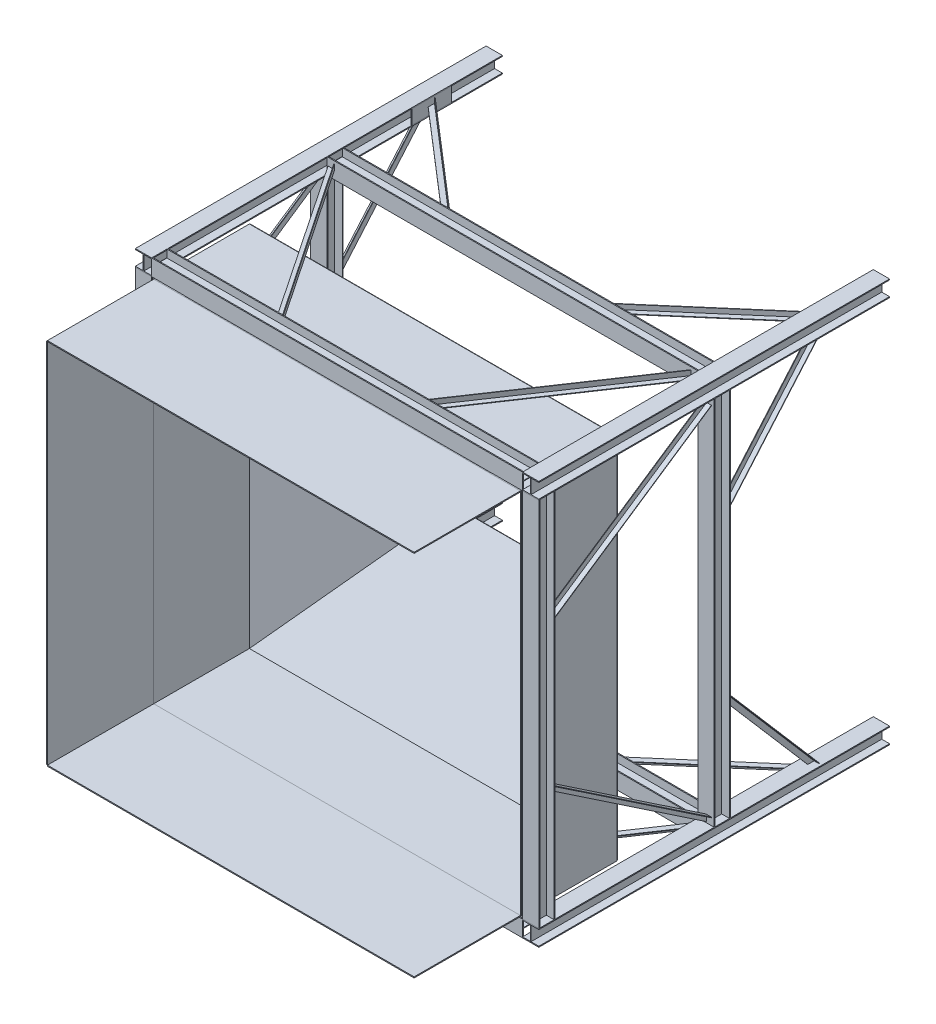
SolidWorks part; units mm, degrees
other "DetailItem1"
other "DetailItem2"
other "DetailItem3"
other "DetailItem4"
other "DetailItem5"
other "DetailItem6"
other "DetailItem7"
other "DetailItem8"
other "DetailItem9"
other "DetailItem10"
other "DetailItem11"
other "DetailItem12"
other "DetailItem13"
other "DetailItem14"
other "DetailItem15"
other "DetailItem16"
other "DetailItem17"
other "DetailItem18"
other "DetailItem19"
other "DetailItem20"
other "DetailItem21"
other "DetailItem22"
other "DetailItem23"
other "DetailItem24"
other "DetailItem25"
other "DetailItem26"
other "DetailItem27"
other "DetailItem28"
other "DetailItem29"
other "DetailItem30"
other "DetailItem31"
other "DetailItem32"
other "DetailItem33"
other "DetailItem34"
other "DetailItem35"
other "DetailItem36"
other "DetailItem37"
other "DetailItem38"
other "DetailItem39"
other "DetailItem40"
other "DetailItem41"
other "DetailItem42"
other "DetailItem43"
other "DetailItem44"
other "DetailItem45"
other "DetailItem46"
other "DetailItem47"
other "DetailItem48"
other "DetailItem49"
other "DetailItem50"
other "DetailItem51"
other "DetailItem52"
other "DetailItem53"
other "DetailItem54"
other "DetailItem55"
other "DetailItem56"
other "DetailItem57"
other "DetailItem58"
other "DetailItem59"
other "DetailItem60"
other "DetailItem61"
other "DetailItem62"
other "DetailItem63"
other "DetailItem64"
other "DetailItem65"
other "DetailItem66"
other "DetailItem67"
other "DetailItem68"
other "DetailItem69"
other "DetailItem70"
other "DetailItem71"
other "DetailItem72"
other "DetailItem73"
other "Carpeta de soldadura"
other "Cordón de soldadura1"
other "Soldadura Viga H carga 1650 B"
other "Soldadura Viga H carga 3300 A"
other "Soldadura Viga H carga 3300 B"
other "Soldadura asiento a tolva carga"
other "Soldadura asiento a bastidor carga"
other "Soldadura Viga H fondo 1650 A"
other "Soldadura Viga H fondo 1650 B"
other "Soldadura Viga H fondo 3300 A"
other "Soldadura Viga H fondo 3300 B"
other "Soldadura asiento a tolva fondo"
other "Soldadura asiento a bastidor fondo"
other "Soldadura Viga H izquierda 1650 A"
other "Soldadura Viga H izquierda 1650 B"
other "Soldadura Viga H izquierda 3300 A"
other "Soldadura Viga H izquierda 3300 B"
other "Soldadura asiento a tolva izquierda"
other "Soldadura asiento a bastidor izquierda"
other "Soldadura Viga H derecha 1650 A"
other "Soldadura Viga H derecha 1650 B"
other "Soldadura Viga H derecha 3300 A"
other "Soldadura Viga H derecha 3300 B"
other "Soldadura asiento a tolva derecha"
other "Soldadura asiento a bastidor derecha"
other "Soldadura Angular superior carga A inferior"
other "Soldadura Angular superior carga A superior"
other "Soldadura Angular inferior carga A inferior"
other "Soldadura Angular inferior carga A superior"
other "Soldadura Angular superior carga B inferior"
other "Soldadura Angular superior carga B superior"
other "Soldadura Angular inferior carga B inferior"
other "Soldadura Angular inferior carga B superior"
other "Soldadura Angular superior fondo A inferior"
other "Soldadura Angular superior fondo A superior"
other "Soldadura Angular inferior fondo A inferior"
other "Soldadura Angular inferior fondo A superior"
other "Soldadura Angular superior fondo B inferior"
other "Soldadura Angular superior fondo B superior"
other "Soldadura Angular inferior fondo B inferior"
other "Soldadura Angular inferior fondo B superior"
other "Soldadura Angular superior izquierda A inferior"
other "Soldadura Angular superior izquierda A superior"
other "Soldadura Angular inferior izquierda A inferior"
other "Soldadura Angular inferior izquierda A superior"
other "Soldadura Angular superior izquierda B inferior"
other "Soldadura Angular superior izquierda B superior"
other "Soldadura Angular inferior izquierda B inferior"
other "Soldadura Angular inferior izquierda B superior"
other "Soldadura Angular superior derecha A inferior"
other "Soldadura Angular superior derecha A superior"
other "Soldadura Angular inferior derecha A inferior"
other "Soldadura Angular inferior derecha A superior"
other "Soldadura Angular superior derecha B inferior"
other "Soldadura Angular superior derecha B superior"
other "Soldadura Angular inferior derecha B inferior"
other "Soldadura Angular inferior derecha B superior"
other "Soldadura alerón a collar lateral Y negativo"
other "Soldadura esquina del collar lateral Y negativo"
other "Soldadura quiebre del embudo lateral Y negativo"
other "Soldadura arista inclinada lateral Y negativo"
other "Soldadura esquina del collar carga"
other "Soldadura quiebre del embudo carga"
other "Soldadura arista inclinada carga"
other "Soldadura alerón a collar lateral Y positivo"
other "Soldadura esquina del collar lateral Y positivo"
other "Soldadura quiebre del embudo lateral Y positivo"
other "Soldadura arista inclinada lateral Y positivo"
other "Soldadura alerón a collar fondo X negativo"
other "Soldadura esquina del collar fondo X negativo"
other "Soldadura quiebre del embudo fondo X negativo"
other "Soldadura arista inclinada fondo X negativo"
other "Soldadura esquina alerones fondo Y positivo"
other "Soldadura esquina alerones fondo Y negativo"
material "ASTM A36 Steel"
ref_plane "Front Plane" through (0, 0, 0) normal (0, 0, 1) x (1, 0, 0)
ref_plane "Top Plane" through (0, 0, 0) normal (0, 1, 0) x (1, 0, 0)
ref_plane "Right Plane" through (0, 0, 0) normal (1, 0, 0) x (0, 0, -1)
sketch3d "Referencias 1"
  point P0 (0, 0, 0)
  point P1 (0, -190, 0)
  point P2 (200, 0, 0)
ref_plane "Plano de perfil 1 estructura" through (0, 0, 0) normal (0, 0, 1) x (1, 0, 0)
sketch "Contorno Columna H 1" plane through (0, 0, 0) normal (0, 0, 1) x (1, 0, 0)
  line L0 (-1898, -1898) -> (-1745, -1898)
  line L1 (-1745, -1898) -> (-1745, -1889)
  line L2 (-1745, -1889) -> (-1818.25, -1889)
  line L3 (-1818.25, -1889) -> (-1818.25, -1754)
  line L4 (-1818.25, -1754) -> (-1745, -1754)
  line L5 (-1745, -1754) -> (-1745, -1745)
  line L6 (-1745, -1745) -> (-1898, -1745)
  line L7 (-1898, -1745) -> (-1898, -1754)
  line L8 (-1898, -1754) -> (-1824.75, -1754)
  line L9 (-1824.75, -1754) -> (-1824.75, -1889)
  line L10 (-1824.75, -1889) -> (-1898, -1889)
  line L11 (-1898, -1889) -> (-1898, -1898)
extrude "Columna H 1" add sketch "Contorno Columna H 1" along normal blind 3300 separate body
sketch "Contorno Columna H 2" plane through (0, 0, 0) normal (0, 0, 1) x (1, 0, 0)
  line L0 (-1898, 1745) -> (-1745, 1745)
  line L1 (-1745, 1745) -> (-1745, 1754)
  line L2 (-1745, 1754) -> (-1818.25, 1754)
  line L3 (-1818.25, 1754) -> (-1818.25, 1889)
  line L4 (-1818.25, 1889) -> (-1745, 1889)
  line L5 (-1745, 1889) -> (-1745, 1898)
  line L6 (-1745, 1898) -> (-1898, 1898)
  line L7 (-1898, 1898) -> (-1898, 1889)
  line L8 (-1898, 1889) -> (-1824.75, 1889)
  line L9 (-1824.75, 1889) -> (-1824.75, 1754)
  line L10 (-1824.75, 1754) -> (-1898, 1754)
  line L11 (-1898, 1754) -> (-1898, 1745)
extrude "Columna H 2" add sketch "Contorno Columna H 2" along normal blind 3300 separate body
sketch "Contorno Columna H 3" plane through (0, 0, 0) normal (0, 0, 1) x (1, 0, 0)
  line L0 (1745, -1898) -> (1898, -1898)
  line L1 (1898, -1898) -> (1898, -1889)
  line L2 (1898, -1889) -> (1824.75, -1889)
  line L3 (1824.75, -1889) -> (1824.75, -1754)
  line L4 (1824.75, -1754) -> (1898, -1754)
  line L5 (1898, -1754) -> (1898, -1745)
  line L6 (1898, -1745) -> (1745, -1745)
  line L7 (1745, -1745) -> (1745, -1754)
  line L8 (1745, -1754) -> (1818.25, -1754)
  line L9 (1818.25, -1754) -> (1818.25, -1889)
  line L10 (1818.25, -1889) -> (1745, -1889)
  line L11 (1745, -1889) -> (1745, -1898)
extrude "Columna H 3" add sketch "Contorno Columna H 3" along normal blind 3300 separate body
sketch "Contorno Columna H 4" plane through (0, 0, 0) normal (0, 0, 1) x (1, 0, 0)
  line L0 (1745, 1745) -> (1898, 1745)
  line L1 (1898, 1745) -> (1898, 1754)
  line L2 (1898, 1754) -> (1824.75, 1754)
  line L3 (1824.75, 1754) -> (1824.75, 1889)
  line L4 (1824.75, 1889) -> (1898, 1889)
  line L5 (1898, 1889) -> (1898, 1898)
  line L6 (1898, 1898) -> (1745, 1898)
  line L7 (1745, 1898) -> (1745, 1889)
  line L8 (1745, 1889) -> (1818.25, 1889)
  line L9 (1818.25, 1889) -> (1818.25, 1754)
  line L10 (1818.25, 1754) -> (1745, 1754)
  line L11 (1745, 1754) -> (1745, 1745)
extrude "Columna H 4" add sketch "Contorno Columna H 4" along normal blind 3300 separate body
sketch3d "Referencias 2"
  point P0 (-1745, 0, 0)
  point P1 (-1745, 190, 0)
  point P2 (-1745, 0, 200)
ref_plane "Plano de perfil 2 estructura" through (-1745, 0, 0) normal (1, 0, 0) x (0, 0, -1)
sketch "Contorno Viga H carga 1650" plane through (-1745, 0, 0) normal (1, 0, 0) x (0, 0, -1)
  line L0 (-1497, -1745) -> (-1497, -1898)
  line L1 (-1497, -1898) -> (-1506, -1898)
  line L2 (-1506, -1898) -> (-1506, -1824.75)
  line L3 (-1506, -1824.75) -> (-1641, -1824.75)
  line L4 (-1641, -1824.75) -> (-1641, -1898)
  line L5 (-1641, -1898) -> (-1650, -1898)
  line L6 (-1650, -1898) -> (-1650, -1745)
  line L7 (-1650, -1745) -> (-1641, -1745)
  line L8 (-1641, -1745) -> (-1641, -1818.25)
  line L9 (-1641, -1818.25) -> (-1506, -1818.25)
  line L10 (-1506, -1818.25) -> (-1506, -1745)
  line L11 (-1506, -1745) -> (-1497, -1745)
extrude "Viga H carga 1650" add sketch "Contorno Viga H carga 1650" along normal blind 3490 separate body
sketch "Contorno Viga H carga 3300" plane through (-1745, 0, 0) normal (1, 0, 0) x (0, 0, -1)
  line L0 (-3147, -1745) -> (-3147, -1898)
  line L1 (-3147, -1898) -> (-3156, -1898)
  line L2 (-3156, -1898) -> (-3156, -1824.75)
  line L3 (-3156, -1824.75) -> (-3291, -1824.75)
  line L4 (-3291, -1824.75) -> (-3291, -1898)
  line L5 (-3291, -1898) -> (-3300, -1898)
  line L6 (-3300, -1898) -> (-3300, -1745)
  line L7 (-3300, -1745) -> (-3291, -1745)
  line L8 (-3291, -1745) -> (-3291, -1818.25)
  line L9 (-3291, -1818.25) -> (-3156, -1818.25)
  line L10 (-3156, -1818.25) -> (-3156, -1745)
  line L11 (-3156, -1745) -> (-3147, -1745)
extrude "Viga H carga 3300" add sketch "Contorno Viga H carga 3300" along normal blind 3490 separate body
sketch "Contorno Cierre columna carga A" plane through (-1745, 0, 0) normal (1, 0, 0) x (0, 0, -1)
  line L0 (-480, -1754) -> (-480, -1889)
  line L1 (-480, -1889) -> (-850, -1889)
  line L2 (-850, -1889) -> (-850, -1754)
  line L3 (-850, -1754) -> (-480, -1754)
extrude "Cierre columna carga A" add sketch "Contorno Cierre columna carga A" against normal blind 8 separate body
sketch3d "Referencias 3"
  point P0 (0, -1821.5, 0)
  point P1 (-190, -1821.5, 0)
  point P2 (0, -1821.5, 200)
ref_plane "Plano de perfil 3 estructura" through (0, -1821.5, 0) normal (0, 1, 0) x (1, 0, 0)
sketch "Contorno Ala plana Angular superior carga A" plane through (0, -1821.5, 0) normal (0, 1, 0) x (1, 0, 0)
  line L0 (-1674.8701, -1650) -> (-1735.1299, -1650)
  line L1 (-1735.1299, -1650) -> (-728.1299, -3147)
  line L2 (-728.1299, -3147) -> (-667.8701, -3147)
  line L3 (-667.8701, -3147) -> (-1674.8701, -1650)
extrude "Ala plana Angular superior carga A" add sketch "Contorno Ala plana Angular superior carga A" against normal blind 5 separate body
sketch3d "Referencias 4"
  point P0 (0, -1826.5, 0)
  point P1 (-190, -1826.5, 0)
  point P2 (0, -1826.5, 200)
ref_plane "Plano de perfil 4 estructura" through (0, -1826.5, 0) normal (0, 1, 0) x (1, 0, 0)
sketch "Contorno Retorno Angular superior carga A" plane through (0, -1826.5, 0) normal (0, 1, 0) x (1, 0, 0)
  line L0 (-1674.8701, -1650) -> (-1680.8961, -1650)
  line L1 (-1680.8961, -1650) -> (-673.8961, -3147)
  line L2 (-673.8961, -3147) -> (-667.8701, -3147)
  line L3 (-667.8701, -3147) -> (-1674.8701, -1650)
extrude "Retorno Angular superior carga A" add sketch "Contorno Retorno Angular superior carga A" against normal blind 45 separate body
combine bodies "Angular superior carga A" operation type add bodies to combine 108 109
sketch "Contorno Ala plana Angular inferior carga A" plane through (0, -1821.5, 0) normal (0, 1, 0) x (1, 0, 0)
  line L0 (-1745, -631.991) -> (-1745, -698.009)
  line L1 (-1745, -698.009) -> (-818.2856, -1497)
  line L2 (-818.2856, -1497) -> (-741.7144, -1497)
  line L3 (-741.7144, -1497) -> (-1745, -631.991)
extrude "Ala plana Angular inferior carga A" add sketch "Contorno Ala plana Angular inferior carga A" against normal blind 5 separate body
sketch "Contorno Retorno Angular inferior carga A" plane through (0, -1826.5, 0) normal (0, 1, 0) x (1, 0, 0)
  line L0 (-1745, -631.991) -> (-1745, -638.5928)
  line L1 (-1745, -638.5928) -> (-749.3715, -1497)
  line L2 (-749.3715, -1497) -> (-741.7144, -1497)
  line L3 (-741.7144, -1497) -> (-1745, -631.991)
extrude "Retorno Angular inferior carga A" add sketch "Contorno Retorno Angular inferior carga A" against normal blind 45 separate body
combine bodies "Angular inferior carga A" operation type add bodies to combine 111 112
sketch3d "Referencias 5"
  point P0 (1745, 0, 0)
  point P1 (1745, 190, 0)
  point P2 (1745, 0, 200)
ref_plane "Plano de perfil 5 estructura" through (1745, 0, 0) normal (1, 0, 0) x (0, 0, -1)
sketch "Contorno Cierre columna carga B" plane through (1745, 0, 0) normal (1, 0, 0) x (0, 0, -1)
  line L0 (-480, -1754) -> (-480, -1889)
  line L1 (-480, -1889) -> (-850, -1889)
  line L2 (-850, -1889) -> (-850, -1754)
  line L3 (-850, -1754) -> (-480, -1754)
extrude "Cierre columna carga B" add sketch "Contorno Cierre columna carga B" along normal blind 8 separate body
sketch "Contorno Ala plana Angular superior carga B" plane through (0, -1821.5, 0) normal (0, 1, 0) x (1, 0, 0)
  line L0 (1674.8701, -1650) -> (1735.1299, -1650)
  line L1 (1735.1299, -1650) -> (728.1299, -3147)
  line L2 (728.1299, -3147) -> (667.8701, -3147)
  line L3 (667.8701, -3147) -> (1674.8701, -1650)
extrude "Ala plana Angular superior carga B" add sketch "Contorno Ala plana Angular superior carga B" against normal blind 5 separate body
sketch "Contorno Retorno Angular superior carga B" plane through (0, -1826.5, 0) normal (0, 1, 0) x (1, 0, 0)
  line L0 (1674.8701, -1650) -> (1680.8961, -1650)
  line L1 (1680.8961, -1650) -> (673.8961, -3147)
  line L2 (673.8961, -3147) -> (667.8701, -3147)
  line L3 (667.8701, -3147) -> (1674.8701, -1650)
extrude "Retorno Angular superior carga B" add sketch "Contorno Retorno Angular superior carga B" against normal blind 45 separate body
combine bodies "Angular superior carga B" operation type add bodies to combine 115 116
sketch "Contorno Ala plana Angular inferior carga B" plane through (0, -1821.5, 0) normal (0, 1, 0) x (1, 0, 0)
  line L0 (1745, -631.991) -> (1745, -698.009)
  line L1 (1745, -698.009) -> (818.2856, -1497)
  line L2 (818.2856, -1497) -> (741.7144, -1497)
  line L3 (741.7144, -1497) -> (1745, -631.991)
extrude "Ala plana Angular inferior carga B" add sketch "Contorno Ala plana Angular inferior carga B" against normal blind 5 separate body
sketch "Contorno Retorno Angular inferior carga B" plane through (0, -1826.5, 0) normal (0, 1, 0) x (1, 0, 0)
  line L0 (1745, -631.991) -> (1745, -638.5928)
  line L1 (1745, -638.5928) -> (749.3715, -1497)
  line L2 (749.3715, -1497) -> (741.7144, -1497)
  line L3 (741.7144, -1497) -> (1745, -631.991)
extrude "Retorno Angular inferior carga B" add sketch "Contorno Retorno Angular inferior carga B" against normal blind 45 separate body
combine bodies "Angular inferior carga B" operation type add bodies to combine 118 119
sketch3d "Referencias 6"
  point P0 (0, 0, 3281.475)
  point P1 (0, -190, 3281.475)
  point P2 (200, 0, 3281.475)
ref_plane "Plano de perfil 6 estructura" through (0, 0, 3281.475) normal (0, 0, 1) x (1, 0, 0)
sketch "Contorno Asiento soldado carga" plane through (0, 0, 3281.475) normal (0, 0, 1) x (1, 0, 0)
  line L0 (-1450, -1734.525) -> (1450, -1734.525)
  line L1 (1450, -1734.525) -> (1450, -1818.25)
  line L2 (1450, -1818.25) -> (-1450, -1818.25)
  line L3 (-1450, -1818.25) -> (-1450, -1734.525)
extrude "Asiento soldado carga" add sketch "Contorno Asiento soldado carga" along normal blind 9.525 separate body
sketch "Contorno Viga H fondo 1650" plane through (-1745, 0, 0) normal (1, 0, 0) x (0, 0, -1)
  line L0 (-1497, 1745) -> (-1497, 1898)
  line L1 (-1497, 1898) -> (-1506, 1898)
  line L2 (-1506, 1898) -> (-1506, 1824.75)
  line L3 (-1506, 1824.75) -> (-1641, 1824.75)
  line L4 (-1641, 1824.75) -> (-1641, 1898)
  line L5 (-1641, 1898) -> (-1650, 1898)
  line L6 (-1650, 1898) -> (-1650, 1745)
  line L7 (-1650, 1745) -> (-1641, 1745)
  line L8 (-1641, 1745) -> (-1641, 1818.25)
  line L9 (-1641, 1818.25) -> (-1506, 1818.25)
  line L10 (-1506, 1818.25) -> (-1506, 1745)
  line L11 (-1506, 1745) -> (-1497, 1745)
extrude "Viga H fondo 1650" add sketch "Contorno Viga H fondo 1650" along normal blind 3490 separate body
sketch "Contorno Viga H fondo 3300" plane through (-1745, 0, 0) normal (1, 0, 0) x (0, 0, -1)
  line L0 (-3147, 1745) -> (-3147, 1898)
  line L1 (-3147, 1898) -> (-3156, 1898)
  line L2 (-3156, 1898) -> (-3156, 1824.75)
  line L3 (-3156, 1824.75) -> (-3291, 1824.75)
  line L4 (-3291, 1824.75) -> (-3291, 1898)
  line L5 (-3291, 1898) -> (-3300, 1898)
  line L6 (-3300, 1898) -> (-3300, 1745)
  line L7 (-3300, 1745) -> (-3291, 1745)
  line L8 (-3291, 1745) -> (-3291, 1818.25)
  line L9 (-3291, 1818.25) -> (-3156, 1818.25)
  line L10 (-3156, 1818.25) -> (-3156, 1745)
  line L11 (-3156, 1745) -> (-3147, 1745)
extrude "Viga H fondo 3300" add sketch "Contorno Viga H fondo 3300" along normal blind 3490 separate body
sketch "Contorno Cierre columna fondo A" plane through (-1745, 0, 0) normal (1, 0, 0) x (0, 0, -1)
  line L0 (-480, 1754) -> (-480, 1889)
  line L1 (-480, 1889) -> (-850, 1889)
  line L2 (-850, 1889) -> (-850, 1754)
  line L3 (-850, 1754) -> (-480, 1754)
extrude "Cierre columna fondo A" add sketch "Contorno Cierre columna fondo A" against normal blind 8 separate body
sketch3d "Referencias 7"
  point P0 (0, 1821.5, 0)
  point P1 (-190, 1821.5, 0)
  point P2 (0, 1821.5, 200)
ref_plane "Plano de perfil 7 estructura" through (0, 1821.5, 0) normal (0, 1, 0) x (1, 0, 0)
sketch "Contorno Ala plana Angular superior fondo A" plane through (0, 1821.5, 0) normal (0, 1, 0) x (1, 0, 0)
  line L0 (-1674.8701, -1650) -> (-1735.1299, -1650)
  line L1 (-1735.1299, -1650) -> (-728.1299, -3147)
  line L2 (-728.1299, -3147) -> (-667.8701, -3147)
  line L3 (-667.8701, -3147) -> (-1674.8701, -1650)
extrude "Ala plana Angular superior fondo A" add sketch "Contorno Ala plana Angular superior fondo A" along normal blind 5 separate body
sketch3d "Referencias 8"
  point P0 (0, 1826.5, 0)
  point P1 (-190, 1826.5, 0)
  point P2 (0, 1826.5, 200)
ref_plane "Plano de perfil 8 estructura" through (0, 1826.5, 0) normal (0, 1, 0) x (1, 0, 0)
sketch "Contorno Retorno Angular superior fondo A" plane through (0, 1826.5, 0) normal (0, 1, 0) x (1, 0, 0)
  line L0 (-1674.8701, -1650) -> (-1680.8961, -1650)
  line L1 (-1680.8961, -1650) -> (-673.8961, -3147)
  line L2 (-673.8961, -3147) -> (-667.8701, -3147)
  line L3 (-667.8701, -3147) -> (-1674.8701, -1650)
extrude "Retorno Angular superior fondo A" add sketch "Contorno Retorno Angular superior fondo A" along normal blind 45 separate body
combine bodies "Angular superior fondo A" operation type add bodies to combine 125 126
sketch "Contorno Ala plana Angular inferior fondo A" plane through (0, 1821.5, 0) normal (0, 1, 0) x (1, 0, 0)
  line L0 (-1745, -631.991) -> (-1745, -698.009)
  line L1 (-1745, -698.009) -> (-818.2856, -1497)
  line L2 (-818.2856, -1497) -> (-741.7144, -1497)
  line L3 (-741.7144, -1497) -> (-1745, -631.991)
extrude "Ala plana Angular inferior fondo A" add sketch "Contorno Ala plana Angular inferior fondo A" along normal blind 5 separate body
sketch "Contorno Retorno Angular inferior fondo A" plane through (0, 1826.5, 0) normal (0, 1, 0) x (1, 0, 0)
  line L0 (-1745, -631.991) -> (-1745, -638.5928)
  line L1 (-1745, -638.5928) -> (-749.3715, -1497)
  line L2 (-749.3715, -1497) -> (-741.7144, -1497)
  line L3 (-741.7144, -1497) -> (-1745, -631.991)
extrude "Retorno Angular inferior fondo A" add sketch "Contorno Retorno Angular inferior fondo A" along normal blind 45 separate body
combine bodies "Angular inferior fondo A" operation type add bodies to combine 128 129
sketch "Contorno Cierre columna fondo B" plane through (1745, 0, 0) normal (1, 0, 0) x (0, 0, -1)
  line L0 (-480, 1754) -> (-480, 1889)
  line L1 (-480, 1889) -> (-850, 1889)
  line L2 (-850, 1889) -> (-850, 1754)
  line L3 (-850, 1754) -> (-480, 1754)
extrude "Cierre columna fondo B" add sketch "Contorno Cierre columna fondo B" along normal blind 8 separate body
sketch "Contorno Ala plana Angular superior fondo B" plane through (0, 1821.5, 0) normal (0, 1, 0) x (1, 0, 0)
  line L0 (1674.8701, -1650) -> (1735.1299, -1650)
  line L1 (1735.1299, -1650) -> (728.1299, -3147)
  line L2 (728.1299, -3147) -> (667.8701, -3147)
  line L3 (667.8701, -3147) -> (1674.8701, -1650)
extrude "Ala plana Angular superior fondo B" add sketch "Contorno Ala plana Angular superior fondo B" along normal blind 5 separate body
sketch "Contorno Retorno Angular superior fondo B" plane through (0, 1826.5, 0) normal (0, 1, 0) x (1, 0, 0)
  line L0 (1674.8701, -1650) -> (1680.8961, -1650)
  line L1 (1680.8961, -1650) -> (673.8961, -3147)
  line L2 (673.8961, -3147) -> (667.8701, -3147)
  line L3 (667.8701, -3147) -> (1674.8701, -1650)
extrude "Retorno Angular superior fondo B" add sketch "Contorno Retorno Angular superior fondo B" along normal blind 45 separate body
combine bodies "Angular superior fondo B" operation type add bodies to combine 132 133
sketch "Contorno Ala plana Angular inferior fondo B" plane through (0, 1821.5, 0) normal (0, 1, 0) x (1, 0, 0)
  line L0 (1745, -631.991) -> (1745, -698.009)
  line L1 (1745, -698.009) -> (818.2856, -1497)
  line L2 (818.2856, -1497) -> (741.7144, -1497)
  line L3 (741.7144, -1497) -> (1745, -631.991)
extrude "Ala plana Angular inferior fondo B" add sketch "Contorno Ala plana Angular inferior fondo B" along normal blind 5 separate body
sketch "Contorno Retorno Angular inferior fondo B" plane through (0, 1826.5, 0) normal (0, 1, 0) x (1, 0, 0)
  line L0 (1745, -631.991) -> (1745, -638.5928)
  line L1 (1745, -638.5928) -> (749.3715, -1497)
  line L2 (749.3715, -1497) -> (741.7144, -1497)
  line L3 (741.7144, -1497) -> (1745, -631.991)
extrude "Retorno Angular inferior fondo B" add sketch "Contorno Retorno Angular inferior fondo B" along normal blind 45 separate body
combine bodies "Angular inferior fondo B" operation type add bodies to combine 135 136
sketch "Contorno Asiento soldado fondo" plane through (0, 0, 3281.475) normal (0, 0, 1) x (1, 0, 0)
  line L0 (-1450, 1734.525) -> (1450, 1734.525)
  line L1 (1450, 1734.525) -> (1450, 1818.25)
  line L2 (1450, 1818.25) -> (-1450, 1818.25)
  line L3 (-1450, 1818.25) -> (-1450, 1734.525)
extrude "Asiento soldado fondo" add sketch "Contorno Asiento soldado fondo" along normal blind 9.525 separate body
sketch3d "Referencias 9"
  point P0 (0, -1745, 0)
  point P1 (-190, -1745, 0)
  point P2 (0, -1745, 200)
ref_plane "Plano de perfil 9 estructura" through (0, -1745, 0) normal (0, 1, 0) x (1, 0, 0)
sketch "Contorno Viga H izquierda 1650" plane through (0, -1745, 0) normal (0, 1, 0) x (1, 0, 0)
  line L0 (-1745, -1497) -> (-1898, -1497)
  line L1 (-1898, -1497) -> (-1898, -1506)
  line L2 (-1898, -1506) -> (-1824.75, -1506)
  line L3 (-1824.75, -1506) -> (-1824.75, -1641)
  line L4 (-1824.75, -1641) -> (-1898, -1641)
  line L5 (-1898, -1641) -> (-1898, -1650)
  line L6 (-1898, -1650) -> (-1745, -1650)
  line L7 (-1745, -1650) -> (-1745, -1641)
  line L8 (-1745, -1641) -> (-1818.25, -1641)
  line L9 (-1818.25, -1641) -> (-1818.25, -1506)
  line L10 (-1818.25, -1506) -> (-1745, -1506)
  line L11 (-1745, -1506) -> (-1745, -1497)
extrude "Viga H izquierda 1650" add sketch "Contorno Viga H izquierda 1650" along normal blind 3490 separate body
sketch "Contorno Viga H izquierda 3300" plane through (0, -1745, 0) normal (0, 1, 0) x (1, 0, 0)
  line L0 (-1745, -3147) -> (-1898, -3147)
  line L1 (-1898, -3147) -> (-1898, -3156)
  line L2 (-1898, -3156) -> (-1824.75, -3156)
  line L3 (-1824.75, -3156) -> (-1824.75, -3291)
  line L4 (-1824.75, -3291) -> (-1898, -3291)
  line L5 (-1898, -3291) -> (-1898, -3300)
  line L6 (-1898, -3300) -> (-1745, -3300)
  line L7 (-1745, -3300) -> (-1745, -3291)
  line L8 (-1745, -3291) -> (-1818.25, -3291)
  line L9 (-1818.25, -3291) -> (-1818.25, -3156)
  line L10 (-1818.25, -3156) -> (-1745, -3156)
  line L11 (-1745, -3156) -> (-1745, -3147)
extrude "Viga H izquierda 3300" add sketch "Contorno Viga H izquierda 3300" along normal blind 3490 separate body
sketch3d "Referencias 10"
  point P0 (-1821.5, 0, 0)
  point P1 (-1821.5, 190, 0)
  point P2 (-1821.5, 0, 200)
ref_plane "Plano de perfil 10 estructura" through (-1821.5, 0, 0) normal (1, 0, 0) x (0, 0, -1)
sketch "Contorno Ala plana Angular superior izquierda A" plane through (-1821.5, 0, 0) normal (1, 0, 0) x (0, 0, -1)
  line L0 (-1650, -1674.8701) -> (-1650, -1735.1299)
  line L1 (-1650, -1735.1299) -> (-3147, -728.1299)
  line L2 (-3147, -728.1299) -> (-3147, -667.8701)
  line L3 (-3147, -667.8701) -> (-1650, -1674.8701)
extrude "Ala plana Angular superior izquierda A" add sketch "Contorno Ala plana Angular superior izquierda A" against normal blind 5 separate body
sketch3d "Referencias 11"
  point P0 (-1826.5, 0, 0)
  point P1 (-1826.5, 190, 0)
  point P2 (-1826.5, 0, 200)
ref_plane "Plano de perfil 11 estructura" through (-1826.5, 0, 0) normal (1, 0, 0) x (0, 0, -1)
sketch "Contorno Retorno Angular superior izquierda A" plane through (-1826.5, 0, 0) normal (1, 0, 0) x (0, 0, -1)
  line L0 (-1650, -1674.8701) -> (-1650, -1680.8961)
  line L1 (-1650, -1680.8961) -> (-3147, -673.8961)
  line L2 (-3147, -673.8961) -> (-3147, -667.8701)
  line L3 (-3147, -667.8701) -> (-1650, -1674.8701)
extrude "Retorno Angular superior izquierda A" add sketch "Contorno Retorno Angular superior izquierda A" against normal blind 45 separate body
combine bodies "Angular superior izquierda A" operation type add bodies to combine 141 142
sketch "Contorno Ala plana Angular inferior izquierda A" plane through (-1821.5, 0, 0) normal (1, 0, 0) x (0, 0, -1)
  line L0 (-631.991, -1745) -> (-698.009, -1745)
  line L1 (-698.009, -1745) -> (-1497, -818.2856)
  line L2 (-1497, -818.2856) -> (-1497, -741.7144)
  line L3 (-1497, -741.7144) -> (-631.991, -1745)
extrude "Ala plana Angular inferior izquierda A" add sketch "Contorno Ala plana Angular inferior izquierda A" against normal blind 5 separate body
sketch "Contorno Retorno Angular inferior izquierda A" plane through (-1826.5, 0, 0) normal (1, 0, 0) x (0, 0, -1)
  line L0 (-631.991, -1745) -> (-638.5928, -1745)
  line L1 (-638.5928, -1745) -> (-1497, -749.3715)
  line L2 (-1497, -749.3715) -> (-1497, -741.7144)
  line L3 (-1497, -741.7144) -> (-631.991, -1745)
extrude "Retorno Angular inferior izquierda A" add sketch "Contorno Retorno Angular inferior izquierda A" against normal blind 45 separate body
combine bodies "Angular inferior izquierda A" operation type add bodies to combine 144 145
sketch "Contorno Ala plana Angular superior izquierda B" plane through (-1821.5, 0, 0) normal (1, 0, 0) x (0, 0, -1)
  line L0 (-1650, 1674.8701) -> (-1650, 1735.1299)
  line L1 (-1650, 1735.1299) -> (-3147, 728.1299)
  line L2 (-3147, 728.1299) -> (-3147, 667.8701)
  line L3 (-3147, 667.8701) -> (-1650, 1674.8701)
extrude "Ala plana Angular superior izquierda B" add sketch "Contorno Ala plana Angular superior izquierda B" against normal blind 5 separate body
sketch "Contorno Retorno Angular superior izquierda B" plane through (-1826.5, 0, 0) normal (1, 0, 0) x (0, 0, -1)
  line L0 (-1650, 1674.8701) -> (-1650, 1680.8961)
  line L1 (-1650, 1680.8961) -> (-3147, 673.8961)
  line L2 (-3147, 673.8961) -> (-3147, 667.8701)
  line L3 (-3147, 667.8701) -> (-1650, 1674.8701)
extrude "Retorno Angular superior izquierda B" add sketch "Contorno Retorno Angular superior izquierda B" against normal blind 45 separate body
combine bodies "Angular superior izquierda B" operation type add bodies to combine 147 148
sketch "Contorno Ala plana Angular inferior izquierda B" plane through (-1821.5, 0, 0) normal (1, 0, 0) x (0, 0, -1)
  line L0 (-631.991, 1745) -> (-698.009, 1745)
  line L1 (-698.009, 1745) -> (-1497, 818.2856)
  line L2 (-1497, 818.2856) -> (-1497, 741.7144)
  line L3 (-1497, 741.7144) -> (-631.991, 1745)
extrude "Ala plana Angular inferior izquierda B" add sketch "Contorno Ala plana Angular inferior izquierda B" against normal blind 5 separate body
sketch "Contorno Retorno Angular inferior izquierda B" plane through (-1826.5, 0, 0) normal (1, 0, 0) x (0, 0, -1)
  line L0 (-631.991, 1745) -> (-638.5928, 1745)
  line L1 (-638.5928, 1745) -> (-1497, 749.3715)
  line L2 (-1497, 749.3715) -> (-1497, 741.7144)
  line L3 (-1497, 741.7144) -> (-631.991, 1745)
extrude "Retorno Angular inferior izquierda B" add sketch "Contorno Retorno Angular inferior izquierda B" against normal blind 45 separate body
combine bodies "Angular inferior izquierda B" operation type add bodies to combine 150 151
sketch "Contorno Asiento soldado izquierda" plane through (0, 0, 3281.475) normal (0, 0, 1) x (1, 0, 0)
  line L0 (-1734.525, -1450) -> (-1734.525, 1450)
  line L1 (-1734.525, 1450) -> (-1818.25, 1450)
  line L2 (-1818.25, 1450) -> (-1818.25, -1450)
  line L3 (-1818.25, -1450) -> (-1734.525, -1450)
extrude "Asiento soldado izquierda" add sketch "Contorno Asiento soldado izquierda" along normal blind 9.525 separate body
sketch "Contorno Viga H derecha 1650" plane through (0, -1745, 0) normal (0, 1, 0) x (1, 0, 0)
  line L0 (1745, -1497) -> (1898, -1497)
  line L1 (1898, -1497) -> (1898, -1506)
  line L2 (1898, -1506) -> (1824.75, -1506)
  line L3 (1824.75, -1506) -> (1824.75, -1641)
  line L4 (1824.75, -1641) -> (1898, -1641)
  line L5 (1898, -1641) -> (1898, -1650)
  line L6 (1898, -1650) -> (1745, -1650)
  line L7 (1745, -1650) -> (1745, -1641)
  line L8 (1745, -1641) -> (1818.25, -1641)
  line L9 (1818.25, -1641) -> (1818.25, -1506)
  line L10 (1818.25, -1506) -> (1745, -1506)
  line L11 (1745, -1506) -> (1745, -1497)
extrude "Viga H derecha 1650" add sketch "Contorno Viga H derecha 1650" along normal blind 3490 separate body
sketch "Contorno Viga H derecha 3300" plane through (0, -1745, 0) normal (0, 1, 0) x (1, 0, 0)
  line L0 (1745, -3147) -> (1898, -3147)
  line L1 (1898, -3147) -> (1898, -3156)
  line L2 (1898, -3156) -> (1824.75, -3156)
  line L3 (1824.75, -3156) -> (1824.75, -3291)
  line L4 (1824.75, -3291) -> (1898, -3291)
  line L5 (1898, -3291) -> (1898, -3300)
  line L6 (1898, -3300) -> (1745, -3300)
  line L7 (1745, -3300) -> (1745, -3291)
  line L8 (1745, -3291) -> (1818.25, -3291)
  line L9 (1818.25, -3291) -> (1818.25, -3156)
  line L10 (1818.25, -3156) -> (1745, -3156)
  line L11 (1745, -3156) -> (1745, -3147)
extrude "Viga H derecha 3300" add sketch "Contorno Viga H derecha 3300" along normal blind 3490 separate body
sketch3d "Referencias 12"
  point P0 (1821.5, 0, 0)
  point P1 (1821.5, 190, 0)
  point P2 (1821.5, 0, 200)
ref_plane "Plano de perfil 12 estructura" through (1821.5, 0, 0) normal (1, 0, 0) x (0, 0, -1)
sketch "Contorno Ala plana Angular superior derecha A" plane through (1821.5, 0, 0) normal (1, 0, 0) x (0, 0, -1)
  line L0 (-1650, -1674.8701) -> (-1650, -1735.1299)
  line L1 (-1650, -1735.1299) -> (-3147, -728.1299)
  line L2 (-3147, -728.1299) -> (-3147, -667.8701)
  line L3 (-3147, -667.8701) -> (-1650, -1674.8701)
extrude "Ala plana Angular superior derecha A" add sketch "Contorno Ala plana Angular superior derecha A" along normal blind 5 separate body
sketch3d "Referencias 13"
  point P0 (1826.5, 0, 0)
  point P1 (1826.5, 190, 0)
  point P2 (1826.5, 0, 200)
ref_plane "Plano de perfil 13 estructura" through (1826.5, 0, 0) normal (1, 0, 0) x (0, 0, -1)
sketch "Contorno Retorno Angular superior derecha A" plane through (1826.5, 0, 0) normal (1, 0, 0) x (0, 0, -1)
  line L0 (-1650, -1674.8701) -> (-1650, -1680.8961)
  line L1 (-1650, -1680.8961) -> (-3147, -673.8961)
  line L2 (-3147, -673.8961) -> (-3147, -667.8701)
  line L3 (-3147, -667.8701) -> (-1650, -1674.8701)
extrude "Retorno Angular superior derecha A" add sketch "Contorno Retorno Angular superior derecha A" along normal blind 45 separate body
combine bodies "Angular superior derecha A" operation type add bodies to combine 156 157
sketch "Contorno Ala plana Angular inferior derecha A" plane through (1821.5, 0, 0) normal (1, 0, 0) x (0, 0, -1)
  line L0 (-631.991, -1745) -> (-698.009, -1745)
  line L1 (-698.009, -1745) -> (-1497, -818.2856)
  line L2 (-1497, -818.2856) -> (-1497, -741.7144)
  line L3 (-1497, -741.7144) -> (-631.991, -1745)
extrude "Ala plana Angular inferior derecha A" add sketch "Contorno Ala plana Angular inferior derecha A" along normal blind 5 separate body
sketch "Contorno Retorno Angular inferior derecha A" plane through (1826.5, 0, 0) normal (1, 0, 0) x (0, 0, -1)
  line L0 (-631.991, -1745) -> (-638.5928, -1745)
  line L1 (-638.5928, -1745) -> (-1497, -749.3715)
  line L2 (-1497, -749.3715) -> (-1497, -741.7144)
  line L3 (-1497, -741.7144) -> (-631.991, -1745)
extrude "Retorno Angular inferior derecha A" add sketch "Contorno Retorno Angular inferior derecha A" along normal blind 45 separate body
combine bodies "Angular inferior derecha A" operation type add bodies to combine 159 160
sketch "Contorno Ala plana Angular superior derecha B" plane through (1821.5, 0, 0) normal (1, 0, 0) x (0, 0, -1)
  line L0 (-1650, 1674.8701) -> (-1650, 1735.1299)
  line L1 (-1650, 1735.1299) -> (-3147, 728.1299)
  line L2 (-3147, 728.1299) -> (-3147, 667.8701)
  line L3 (-3147, 667.8701) -> (-1650, 1674.8701)
extrude "Ala plana Angular superior derecha B" add sketch "Contorno Ala plana Angular superior derecha B" along normal blind 5 separate body
sketch "Contorno Retorno Angular superior derecha B" plane through (1826.5, 0, 0) normal (1, 0, 0) x (0, 0, -1)
  line L0 (-1650, 1674.8701) -> (-1650, 1680.8961)
  line L1 (-1650, 1680.8961) -> (-3147, 673.8961)
  line L2 (-3147, 673.8961) -> (-3147, 667.8701)
  line L3 (-3147, 667.8701) -> (-1650, 1674.8701)
extrude "Retorno Angular superior derecha B" add sketch "Contorno Retorno Angular superior derecha B" along normal blind 45 separate body
combine bodies "Angular superior derecha B" operation type add bodies to combine 162 163
sketch "Contorno Ala plana Angular inferior derecha B" plane through (1821.5, 0, 0) normal (1, 0, 0) x (0, 0, -1)
  line L0 (-631.991, 1745) -> (-698.009, 1745)
  line L1 (-698.009, 1745) -> (-1497, 818.2856)
  line L2 (-1497, 818.2856) -> (-1497, 741.7144)
  line L3 (-1497, 741.7144) -> (-631.991, 1745)
extrude "Ala plana Angular inferior derecha B" add sketch "Contorno Ala plana Angular inferior derecha B" along normal blind 5 separate body
sketch "Contorno Retorno Angular inferior derecha B" plane through (1826.5, 0, 0) normal (1, 0, 0) x (0, 0, -1)
  line L0 (-631.991, 1745) -> (-638.5928, 1745)
  line L1 (-638.5928, 1745) -> (-1497, 749.3715)
  line L2 (-1497, 749.3715) -> (-1497, 741.7144)
  line L3 (-1497, 741.7144) -> (-631.991, 1745)
extrude "Retorno Angular inferior derecha B" add sketch "Contorno Retorno Angular inferior derecha B" along normal blind 45 separate body
combine bodies "Angular inferior derecha B" operation type add bodies to combine 165 166
sketch "Contorno Asiento soldado derecha" plane through (0, 0, 3281.475) normal (0, 0, 1) x (1, 0, 0)
  line L0 (1734.525, -1450) -> (1734.525, 1450)
  line L1 (1734.525, 1450) -> (1818.25, 1450)
  line L2 (1818.25, 1450) -> (1818.25, -1450)
  line L3 (1818.25, -1450) -> (1734.525, -1450)
extrude "Asiento soldado derecha" add sketch "Contorno Asiento soldado derecha" along normal blind 9.525 separate body
sketch3d "Junta Viga H carga 1650 A"
  line L0 (-1745, -1745, 1650) -> (-1745, -1898, 1650)
sketch3d "Junta Viga H carga 1650 B"
  line L0 (1745, -1745, 1650) -> (1745, -1898, 1650)
sketch3d "Junta Viga H carga 3300 A"
  line L0 (-1745, -1745, 3300) -> (-1745, -1898, 3300)
sketch3d "Junta Viga H carga 3300 B"
  line L0 (1745, -1745, 3300) -> (1745, -1898, 3300)
sketch3d "Junta Angular superior carga A inferior"
  line L0 (-1674.8701, -1821.5, 1650) -> (-1735.1299, -1821.5, 1650)
sketch3d "Junta Angular superior carga A superior"
  line L0 (-667.8701, -1821.5, 3147) -> (-728.1299, -1821.5, 3147)
sketch3d "Junta Angular inferior carga A inferior"
  line L0 (-1745, -1821.5, 631.991) -> (-1745, -1821.5, 698.009)
sketch3d "Junta Angular inferior carga A superior"
  line L0 (-741.7144, -1821.5, 1497) -> (-818.2856, -1821.5, 1497)
sketch3d "Junta Angular superior carga B inferior"
  line L0 (1674.8701, -1821.5, 1650) -> (1735.1299, -1821.5, 1650)
sketch3d "Junta Angular superior carga B superior"
  line L0 (667.8701, -1821.5, 3147) -> (728.1299, -1821.5, 3147)
sketch3d "Junta Angular inferior carga B inferior"
  line L0 (1745, -1821.5, 631.991) -> (1745, -1821.5, 698.009)
sketch3d "Junta Angular inferior carga B superior"
  line L0 (741.7144, -1821.5, 1497) -> (818.2856, -1821.5, 1497)
sketch3d "Junta asiento a tolva carga"
  line L0 (-1450, -1734.525, 3281.475) -> (1450, -1734.525, 3281.475)
sketch3d "Junta asiento a bastidor carga"
  line L0 (-1450, -1745, 3291) -> (1450, -1745, 3291)
sketch3d "Junta Viga H fondo 1650 A"
  line L0 (-1745, 1745, 1650) -> (-1745, 1898, 1650)
sketch3d "Junta Viga H fondo 1650 B"
  line L0 (1745, 1745, 1650) -> (1745, 1898, 1650)
sketch3d "Junta Viga H fondo 3300 A"
  line L0 (-1745, 1745, 3300) -> (-1745, 1898, 3300)
sketch3d "Junta Viga H fondo 3300 B"
  line L0 (1745, 1745, 3300) -> (1745, 1898, 3300)
sketch3d "Junta Angular superior fondo A inferior"
  line L0 (-1674.8701, 1821.5, 1650) -> (-1735.1299, 1821.5, 1650)
sketch3d "Junta Angular superior fondo A superior"
  line L0 (-667.8701, 1821.5, 3147) -> (-728.1299, 1821.5, 3147)
sketch3d "Junta Angular inferior fondo A inferior"
  line L0 (-1745, 1821.5, 631.991) -> (-1745, 1821.5, 698.009)
sketch3d "Junta Angular inferior fondo A superior"
  line L0 (-741.7144, 1821.5, 1497) -> (-818.2856, 1821.5, 1497)
sketch3d "Junta Angular superior fondo B inferior"
  line L0 (1674.8701, 1821.5, 1650) -> (1735.1299, 1821.5, 1650)
sketch3d "Junta Angular superior fondo B superior"
  line L0 (667.8701, 1821.5, 3147) -> (728.1299, 1821.5, 3147)
sketch3d "Junta Angular inferior fondo B inferior"
  line L0 (1745, 1821.5, 631.991) -> (1745, 1821.5, 698.009)
sketch3d "Junta Angular inferior fondo B superior"
  line L0 (741.7144, 1821.5, 1497) -> (818.2856, 1821.5, 1497)
sketch3d "Junta asiento a tolva fondo"
  line L0 (-1450, 1734.525, 3281.475) -> (1450, 1734.525, 3281.475)
sketch3d "Junta asiento a bastidor fondo"
  line L0 (-1450, 1745, 3291) -> (1450, 1745, 3291)
sketch3d "Junta Viga H izquierda 1650 A"
  line L0 (-1745, -1745, 1650) -> (-1898, -1745, 1650)
sketch3d "Junta Viga H izquierda 1650 B"
  line L0 (-1745, 1745, 1650) -> (-1898, 1745, 1650)
sketch3d "Junta Viga H izquierda 3300 A"
  line L0 (-1745, -1745, 3300) -> (-1898, -1745, 3300)
sketch3d "Junta Viga H izquierda 3300 B"
  line L0 (-1745, 1745, 3300) -> (-1898, 1745, 3300)
sketch3d "Junta Angular superior izquierda A inferior"
  line L0 (-1821.5, -1674.8701, 1650) -> (-1821.5, -1735.1299, 1650)
sketch3d "Junta Angular superior izquierda A superior"
  line L0 (-1821.5, -667.8701, 3147) -> (-1821.5, -728.1299, 3147)
sketch3d "Junta Angular inferior izquierda A inferior"
  line L0 (-1821.5, -1745, 631.991) -> (-1821.5, -1745, 698.009)
sketch3d "Junta Angular inferior izquierda A superior"
  line L0 (-1821.5, -741.7144, 1497) -> (-1821.5, -818.2856, 1497)
sketch3d "Junta Angular superior izquierda B inferior"
  line L0 (-1821.5, 1674.8701, 1650) -> (-1821.5, 1735.1299, 1650)
sketch3d "Junta Angular superior izquierda B superior"
  line L0 (-1821.5, 667.8701, 3147) -> (-1821.5, 728.1299, 3147)
sketch3d "Junta Angular inferior izquierda B inferior"
  line L0 (-1821.5, 1745, 631.991) -> (-1821.5, 1745, 698.009)
sketch3d "Junta Angular inferior izquierda B superior"
  line L0 (-1821.5, 741.7144, 1497) -> (-1821.5, 818.2856, 1497)
sketch3d "Junta asiento a tolva izquierda"
  line L0 (-1734.525, -1450, 3281.475) -> (-1734.525, 1450, 3281.475)
sketch3d "Junta asiento a bastidor izquierda"
  line L0 (-1745, -1450, 3291) -> (-1745, 1450, 3291)
sketch3d "Junta Viga H derecha 1650 A"
  line L0 (1745, -1745, 1650) -> (1898, -1745, 1650)
sketch3d "Junta Viga H derecha 1650 B"
  line L0 (1745, 1745, 1650) -> (1898, 1745, 1650)
sketch3d "Junta Viga H derecha 3300 A"
  line L0 (1745, -1745, 3300) -> (1898, -1745, 3300)
sketch3d "Junta Viga H derecha 3300 B"
  line L0 (1745, 1745, 3300) -> (1898, 1745, 3300)
sketch3d "Junta Angular superior derecha A inferior"
  line L0 (1821.5, -1674.8701, 1650) -> (1821.5, -1735.1299, 1650)
sketch3d "Junta Angular superior derecha A superior"
  line L0 (1821.5, -667.8701, 3147) -> (1821.5, -728.1299, 3147)
sketch3d "Junta Angular inferior derecha A inferior"
  line L0 (1821.5, -1745, 631.991) -> (1821.5, -1745, 698.009)
sketch3d "Junta Angular inferior derecha A superior"
  line L0 (1821.5, -741.7144, 1497) -> (1821.5, -818.2856, 1497)
sketch3d "Junta Angular superior derecha B inferior"
  line L0 (1821.5, 1674.8701, 1650) -> (1821.5, 1735.1299, 1650)
sketch3d "Junta Angular superior derecha B superior"
  line L0 (1821.5, 667.8701, 3147) -> (1821.5, 728.1299, 3147)
sketch3d "Junta Angular inferior derecha B inferior"
  line L0 (1821.5, 1745, 631.991) -> (1821.5, 1745, 698.009)
sketch3d "Junta Angular inferior derecha B superior"
  line L0 (1821.5, 741.7144, 1497) -> (1821.5, 818.2856, 1497)
sketch3d "Junta asiento a tolva derecha"
  line L0 (1734.525, -1450, 3281.475) -> (1734.525, 1450, 3281.475)
sketch3d "Junta asiento a bastidor derecha"
  line L0 (1745, -1450, 3291) -> (1745, 1450, 3291)
sketch3d "Croquis3D1"
  point P0 (0, -1725, 0)
  point P1 (-190, -1725, 0)
  point P2 (0, -1725, 200)
ref_plane "Plano de perfil 1 tolva" through (0, -1725, 0) normal (0, 1, 0) x (1, 0, 0)
sketch "Contorno Collar lateral Y negativo" plane through (0, -1725, 0) normal (0, 1, 0) x (1, 0, 0)
  line L0 (-1725, -3300) -> (1725, -3300)
  line L1 (1725, -3300) -> (1725, -2400)
  line L2 (1725, -2400) -> (-1725, -2400)
  line L3 (-1725, -2400) -> (-1725, -3300)
extrude "Collar lateral Y negativo" add sketch "Contorno Collar lateral Y negativo" against normal blind 9.525 separate body
sketch "Contorno Alerón lateral Y negativo" plane through (0, -1725, 0) normal (0, 1, 0) x (1, 0, 0)
  line L0 (-1725, -3300) -> (1725, -3300)
  line L1 (1725, -3300) -> (1725, -4300)
  line L2 (1725, -4300) -> (-1725, -4300)
  line L3 (-1725, -4300) -> (-1725, -3300)
extrude "Alerón lateral Y negativo" add sketch "Contorno Alerón lateral Y negativo" against normal blind 9.525 separate body
sketch3d "Croquis3D2"
  point P0 (0, 601.0957, 995.5648)
  point P1 (0, 438.4435, 1093.77)
  point P2 (200, 601.0957, 995.5648)
ref_plane "Plano de perfil 2 tolva" through (0, 601.0957, 995.5648) normal (0, 0.5169, 0.8561) x (1, 0, 0)
sketch "Contorno Embudo lateral Y negativo" plane through (0, 601.0957, 995.5648) normal (0, 0.5169, 0.8561) x (1, 0, 0)
  line L0 (-1725, -2717.197) -> (1725, -2717.197)
  line L1 (1725, -2717.197) -> (600, -1169.4163)
  line L2 (600, -1169.4163) -> (-600, -1169.4163)
  line L3 (-600, -1169.4163) -> (-1725, -2717.197)
extrude "Embudo lateral Y negativo" add sketch "Contorno Embudo lateral Y negativo" against normal blind 9.525 separate body
sketch3d "Croquis3D3"
  point P0 (1725, 0, 0)
  point P1 (1725, 190, 0)
  point P2 (1725, 0, 200)
ref_plane "Plano de perfil 3 tolva" through (1725, 0, 0) normal (1, 0, 0) x (0, 0, -1)
sketch "Contorno Collar carga" plane through (1725, 0, 0) normal (1, 0, 0) x (0, 0, -1)
  line L0 (-3300, -1725) -> (-3300, 1725)
  line L1 (-3300, 1725) -> (-2400, 1725)
  line L2 (-2400, 1725) -> (-2400, -1725)
  line L3 (-2400, -1725) -> (-3300, -1725)
extrude "Collar carga" add sketch "Contorno Collar carga" along normal blind 9.525 separate body
sketch3d "Croquis3D4"
  point P0 (-554.1489, 0, 779.2719)
  point P1 (-554.1489, 190, 779.2719)
  point P2 (-391.1578, 0, 895.1766)
ref_plane "Plano de perfil 4 tolva" through (-554.1489, 0, 779.2719) normal (0.5795, 0, -0.815) x (-0.815, 0, -0.5795)
sketch "Contorno Embudo carga" plane through (-554.1489, 0, 779.2719) normal (0.5795, 0, -0.815) x (-0.815, 0, -0.5795)
  line L0 (-2796.655, -1725) -> (-2796.655, 1725)
  line L1 (-2796.655, 1725) -> (-1416.2113, 400)
  line L2 (-1416.2113, 400) -> (-1416.2113, -400)
  line L3 (-1416.2113, -400) -> (-2796.655, -1725)
extrude "Embudo carga" add sketch "Contorno Embudo carga" along normal blind 9.525 separate body
sketch3d "Croquis3D5"
  point P0 (0, 1725, 0)
  point P1 (-190, 1725, 0)
  point P2 (0, 1725, 200)
ref_plane "Plano de perfil 5 tolva" through (0, 1725, 0) normal (0, 1, 0) x (1, 0, 0)
sketch "Contorno Collar lateral Y positivo" plane through (0, 1725, 0) normal (0, 1, 0) x (1, 0, 0)
  line L0 (1725, -3300) -> (-1725, -3300)
  line L1 (-1725, -3300) -> (-1725, -2400)
  line L2 (-1725, -2400) -> (1725, -2400)
  line L3 (1725, -2400) -> (1725, -3300)
extrude "Collar lateral Y positivo" add sketch "Contorno Collar lateral Y positivo" along normal blind 9.525 separate body
sketch "Contorno Alerón lateral Y positivo" plane through (0, 1725, 0) normal (0, 1, 0) x (1, 0, 0)
  line L0 (1725, -3300) -> (-1725, -3300)
  line L1 (-1725, -3300) -> (-1725, -4300)
  line L2 (-1725, -4300) -> (1725, -4300)
  line L3 (1725, -4300) -> (1725, -3300)
extrude "Alerón lateral Y positivo" add sketch "Contorno Alerón lateral Y positivo" along normal blind 9.525 separate body
sketch3d "Croquis3D6"
  point P0 (0, -601.0957, 995.5648)
  point P1 (0, -438.4435, 1093.77)
  point P2 (200, -601.0957, 995.5648)
ref_plane "Plano de perfil 6 tolva" through (0, -601.0957, 995.5648) normal (0, 0.5169, -0.8561) x (-1, 0, 0)
sketch "Contorno Embudo lateral Y positivo" plane through (0, -601.0957, 995.5648) normal (0, 0.5169, -0.8561) x (-1, 0, 0)
  line L0 (-1725, 2717.197) -> (1725, 2717.197)
  line L1 (1725, 2717.197) -> (600, 1169.4163)
  line L2 (600, 1169.4163) -> (-600, 1169.4163)
  line L3 (-600, 1169.4163) -> (-1725, 2717.197)
extrude "Embudo lateral Y positivo" add sketch "Contorno Embudo lateral Y positivo" along normal blind 9.525 separate body
sketch3d "Croquis3D7"
  point P0 (-1725, 0, 0)
  point P1 (-1725, 190, 0)
  point P2 (-1725, 0, 200)
ref_plane "Plano de perfil 7 tolva" through (-1725, 0, 0) normal (1, 0, 0) x (0, 0, -1)
sketch "Contorno Collar fondo X negativo" plane through (-1725, 0, 0) normal (1, 0, 0) x (0, 0, -1)
  line L0 (-3300, 1725) -> (-3300, -1725)
  line L1 (-3300, -1725) -> (-2400, -1725)
  line L2 (-2400, -1725) -> (-2400, 1725)
  line L3 (-2400, 1725) -> (-3300, 1725)
extrude "Collar fondo X negativo" add sketch "Contorno Collar fondo X negativo" against normal blind 9.525 separate body
sketch "Contorno Alerón fondo X negativo" plane through (-1725, 0, 0) normal (1, 0, 0) x (0, 0, -1)
  line L0 (-3300, 1725) -> (-3300, -1725)
  line L1 (-3300, -1725) -> (-4300, -1725)
  line L2 (-4300, -1725) -> (-4300, 1725)
  line L3 (-4300, 1725) -> (-3300, 1725)
extrude "Alerón fondo X negativo" add sketch "Contorno Alerón fondo X negativo" against normal blind 9.525 separate body
sketch3d "Croquis3D8"
  point P0 (554.1489, 0, 779.2719)
  point P1 (554.1489, -190, 779.2719)
  point P2 (717.14, 0, 663.3671)
ref_plane "Plano de perfil 8 tolva" through (554.1489, 0, 779.2719) normal (0.5795, 0, 0.815) x (0.815, 0, -0.5795)
sketch "Contorno Embudo fondo X negativo" plane through (554.1489, 0, 779.2719) normal (0.5795, 0, 0.815) x (0.815, 0, -0.5795)
  line L0 (-2796.655, 1725) -> (-2796.655, -1725)
  line L1 (-2796.655, -1725) -> (-1416.2113, -400)
  line L2 (-1416.2113, -400) -> (-1416.2113, 400)
  line L3 (-1416.2113, 400) -> (-2796.655, 1725)
extrude "Embudo fondo X negativo" add sketch "Contorno Embudo fondo X negativo" against normal blind 9.525 separate body
sketch3d "Junta alerón a collar lateral Y negativo"
  line L0 (-1725, -1725, 3300) -> (1725, -1725, 3300)
sketch3d "Junta esquina del collar lateral Y negativo"
  line L0 (-1725, -1725, 3300) -> (-1725, -1725, 2400)
sketch3d "Junta quiebre del embudo lateral Y negativo"
  line L0 (-1725, -1725, 2400) -> (1725, -1725, 2400)
sketch3d "Junta arista inclinada lateral Y negativo"
  line L0 (-1725, -1725, 2400) -> (-600, -400, 1600)
sketch3d "Junta esquina del collar carga"
  line L0 (1725, -1725, 3300) -> (1725, -1725, 2400)
sketch3d "Junta quiebre del embudo carga"
  line L0 (1725, -1725, 2400) -> (1725, 1725, 2400)
sketch3d "Junta arista inclinada carga"
  line L0 (1725, -1725, 2400) -> (600, -400, 1600)
sketch3d "Junta alerón a collar lateral Y positivo"
  line L0 (1725, 1725, 3300) -> (-1725, 1725, 3300)
sketch3d "Junta esquina del collar lateral Y positivo"
  line L0 (1725, 1725, 3300) -> (1725, 1725, 2400)
sketch3d "Junta quiebre del embudo lateral Y positivo"
  line L0 (1725, 1725, 2400) -> (-1725, 1725, 2400)
sketch3d "Junta arista inclinada lateral Y positivo"
  line L0 (1725, 1725, 2400) -> (600, 400, 1600)
sketch3d "Junta alerón a collar fondo X negativo"
  line L0 (-1725, 1725, 3300) -> (-1725, -1725, 3300)
sketch3d "Junta esquina del collar fondo X negativo"
  line L0 (-1725, 1725, 3300) -> (-1725, 1725, 2400)
sketch3d "Junta quiebre del embudo fondo X negativo"
  line L0 (-1725, 1725, 2400) -> (-1725, -1725, 2400)
sketch3d "Junta arista inclinada fondo X negativo"
  line L0 (-1725, 1725, 2400) -> (-600, 400, 1600)
sketch3d "Junta esquina alerones fondo Y positivo"
  line L0 (-1725, 1725, 3300) -> (-1725, 1725, 4300)
sketch3d "Junta esquina alerones fondo Y negativo"
  line L0 (-1725, -1725, 3300) -> (-1725, -1725, 4300)
